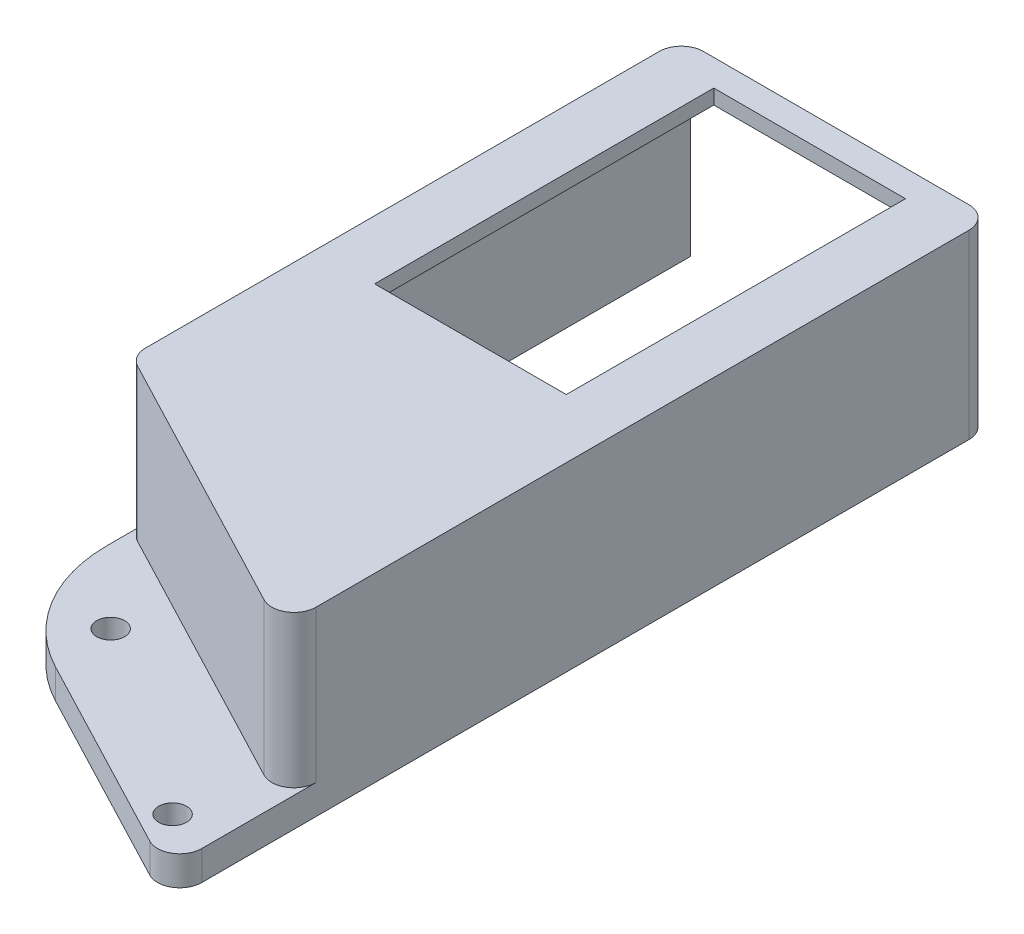
SolidWorks part; units mm, degrees
ref_plane "Front Plane" through (0, 0, 0) normal (0, 0, 1) x (1, 0, 0)
ref_plane "Top Plane" through (0, 0, 0) normal (0, 1, 0) x (1, 0, 0)
ref_plane "Right Plane" through (0, 0, 0) normal (1, 0, 0) x (0, 0, -1)
sketch "Sketch1" plane through (0, 0, 0) normal (0, 1, 0) x (1, 0, 0)
  line L0 (-10.5, 0) -> (10.5, 0)
  line L1 (10.5, 0) -> (10.5, -56)
  line L2 (10.5, -56) -> (-10.5, -45)
  line L3 (-10.5, -45) -> (-10.5, 0)
  line L4 (-10.5, -37.2506) -> (10.5, -48.2506)
  line L5 (-10.5, 0) -> (-9.7, 0)
  line L6 (-10.5, 0) -> (-10.5, -36.4899)
  line L7 (-10.5, -36.4899) -> (-9.7, -36.4899)
  line L8 (-9.7, 0) -> (-9.7, -36.4899)
  line L9 (10.5, 0) -> (9.7, 0)
  line L10 (10.5, 0) -> (10.5, -46.642)
  line L11 (10.5, -46.642) -> (9.7, -46.642)
  line L12 (9.7, 0) -> (9.7, -46.642)
  line L13 (-6.5, -1.8007) -> (6.5, -1.8007)
  line L14 (-6.5, -1.8007) -> (-6.5, -24.8007)
  line L15 (-6.5, -24.8007) -> (6.5, -24.8007)
  line L16 (6.5, -1.8007) -> (6.5, -24.8007)
  line L17 (10.5, -48.2506) -> (10.5, -46.5741)
  line L18 (10.5, -46.5741) -> (-10.5, -35.5741)
  line L19 (-10.5, -35.5741) -> (-10.5, -37.2506)
  circle A2 centre (7.5, -52.5) radius 0.9463
  circle A3 centre (-5.5, -43.7) radius 0.9463
  point P2 (0, 0)
  point P13 (-9.7, -36.4899)
  point P15 (9.7, -46.642)
  point P23 (0, -1.8007)
  dimension "D10" = 1.8926
  dimension "D1" = 56
  dimension "D2" = 45
  dimension "D3" = 21
  dimension "D4" = 43.7
  dimension "D5" = 52.5
  dimension "D6" = 0.8
  dimension "D7" = 0.8
  dimension "D8" = 3
  dimension "D9" = 16
  dimension "D12" = 13
  dimension "D14" = 1.8007
  dimension "D16" = 23
  dimension "D17" = 7.7494
  dimension "D18" = 1.6766
extrude "Boss-Extrude1" add sketch "Sketch1" against normal blind 12.3 contours L18 L1 L0 L12 | L18 L8 L0 L6 region at (-10.0992, 0, 17.892) region at (10.1006, 0, 23.1824)
extrude "Boss-Extrude2" add sketch "Sketch1<3>" against normal blind 1 contours L18 L1 L11 L12 L0 L8 L7 L3 L13 L16 L15 L14 | L1 L18 L3 L4 region at (0.6402, 0, 25.0509) region at (0.102, 0, 41.9779)
sketch "Sketch1<3>" plane through (0, 0, 0) normal (0, 1, 0) x (1, 0, 0) same geometry as "Sketch1"
extrude "Boss-Extrude3" add sketch "Sketch1<4>" against normal blind 12.3 contours L4 L3 L2 L1 | A3 | A2 | L18 L19 L4 L17 region at (-0.0358, 0, 46.5725)
sketch "Sketch1<4>" plane through (0, 0, 0) normal (0, 1, 0) x (1, 0, 0) same geometry as "Sketch1"
extrude "Cut-Extrude2" cut sketch "Sketch1<6>" against normal blind 10.3 contours L4 L3 L2 L1 | A3 | A2 region at (-0.0358, 0, 46.5725)
sketch "Sketch1<6>" plane through (0, 0, 0) normal (0, 1, 0) x (1, 0, 0) same geometry as "Sketch1"
fillet "Fillet1" radius 10 1 edges at (-10.5, -11.3, 45)
fillet "Fillet2" radius 1.5 5 edges at (10.5, -6.15, 0) (10.5, -11.3, 56) (10.5, -5.15, 48.2506) (-10.5, -6.15, 0) (-10.5, -5.15, 37.2506)
